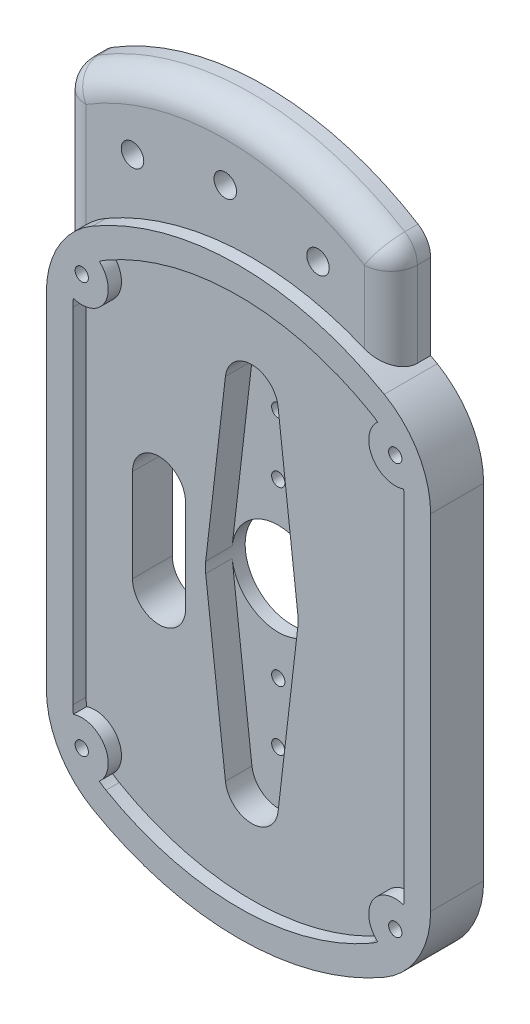
SolidWorks part; units mm, degrees
ref_plane "Спереди" through (0, 0, 0) normal (0, 0, 1) x (1, 0, 0)
ref_plane "Сверху" through (0, 0, 0) normal (0, 1, 0) x (1, 0, 0)
ref_plane "Справа" through (0, 0, 0) normal (1, 0, 0) x (0, 0, -1)
other "Configuration Table"
sketch "Эскиз1" plane through (0, 0, 0) normal (0, 0, 1) x (1, 0, 0)
  line L0 (-6.9532, 0.8077) -> (-3.9733, 26.4615)
  line L1 (3.9733, 26.4615) -> (6.9532, 0.8077)
  line L2 (0, 0) -> (45.5285, 0) construction
  line L3 (3.9733, -26.4615) -> (6.9532, -0.8077)
  line L4 (-6.9532, -0.8077) -> (-3.9733, -26.4615)
  line L5 (25, 25.9808) -> (25, -25.9808)
  line L6 (-25, -25.9808) -> (-25, 25.9808)
  line L7 (0, 0) -> (0, 67.5553) construction
  line L8 (-29, -25.9808) -> (-29, 25.9808)
  line L9 (29, 25.9808) -> (29, -25.9808)
  line L10 (-29, 25.9808) -> (-29, 53.6652)
  line L12 (21, 53.6652) -> (21, 38.6652)
  arc A0 (6.9532, -0.8077) -> (6.9532, 0.8077) centre (0, 0) ccw
  arc A1 (3.9733, 26.4615) -> (-3.9733, 26.4615) centre (0, 26) ccw
  arc A2 (-3.9733, -26.4615) -> (3.9733, -26.4615) centre (0, -26) ccw
  arc A3 (-6.9532, 0.8077) -> (-6.9532, -0.8077) centre (0, 0) ccw
  circle A4 centre (0, 0) radius 7
  circle A5 centre (0, 13) radius 1
  circle A6 centre (0, 22) radius 1
  circle A7 centre (0, -13) radius 1
  circle A8 centre (0, -22) radius 1
  arc A9 (-20, -34.641) -> (20, -34.641) centre (0, 0) ccw
  arc A10 (20, 34.641) -> (-20, 34.641) centre (0, 0) ccw
  arc A11 (-25, -25.9808) -> (-20, -34.641) centre (-15, -25.9808) ccw
  arc A12 (25, -25.9808) -> (20, -34.641) centre (15, -25.9808) cw
  arc A13 (25, 25.9808) -> (20, 34.641) centre (15, 25.9808) ccw
  arc A14 (-25, 25.9808) -> (-20, 34.641) centre (-15, 25.9808) cw
  arc A15 (-29, 25.9808) -> (-22, 38.1051) centre (-15, 25.9808) cw
  arc A16 (22, 38.1051) -> (-22, 38.1051) centre (0, 0) ccw
  arc A17 (29, 25.9808) -> (22, 38.1051) centre (15, 25.9808) ccw
  arc A18 (29, -25.9808) -> (22, -38.1051) centre (15, -25.9808) cw
  arc A19 (-22, -38.1051) -> (22, -38.1051) centre (0, 0) ccw
  arc A20 (-29, -25.9808) -> (-22, -38.1051) centre (-15, -25.9808) ccw
  circle A24 centre (-23.6603, 30.9808) radius 4
  circle A25 centre (23.6603, 30.9808) radius 4
  circle A26 centre (-23.6603, -30.9808) radius 4
  circle A27 centre (23.6603, -30.9808) radius 4
  circle A28 centre (-23.6603, 30.9808) radius 1
  circle A29 centre (23.6603, 30.9808) radius 1
  circle A30 centre (23.6603, -30.9808) radius 1
  circle A31 centre (-23.6603, -30.9808) radius 1
  arc A32 (-29, 53.6652) -> (21, 53.6652) centre (-4, 17.4575) cw
  point P33 (25, 31.225)
  dimension "D1" = 14
  dimension "D2" = 8
  dimension "D6" = 2
  dimension "D7" = 80
  dimension "D9" = 10
  dimension "D11" = 2
  dimension "D3" = 52
  dimension "D4" = 9
  dimension "D5" = 13
  dimension "D8" = 50
  dimension "D12" = 50
  dimension "D13" = 15
  dimension "D10" = 4
extrude "Бобышка-Вытянуть1" add sketch "Эскиз1" along normal blind 6 contours A14 L6 A11 A9 A12 L5 A13 A10 A3 L0 A1 L1 A0 L3 A2 L4 region at (24.0566, 0, 0)
extrude "Бобышка-Вытянуть2" add sketch "Эскиз1<3>" along normal blind 2 contours A4 L1 A1 L0 A6 A5 | A4 L4 A2 L3 A7 A8 region at (0, 16.3649, 0) region at (0, -16.3649, 0)
sketch "Эскиз1<3>" plane through (0, 0, 0) normal (0, 0, 1) x (1, 0, 0) same geometry as "Эскиз1"
extrude "Бобышка-Вытянуть3" add sketch "Эскиз1<4>" along normal blind 8 contours A31 A11 A26 | A31 A11 A26 | A26 A11 L6 A14 A24 A15 L8 A20 | A27 A12 A9 A11 A26 A20 A19 A18 | A30 A12 A27 | A30 A12 A27 | A27 A18 L9 A17 A25 A13 L5 A12 | A29 A13 A25 | A29 A13 A25 | A25 A17 A16 A15 A24 A14 A10 A13 | A28 A14 A24 | A28 A14 A24 region at (27.0355, 0, 0) region at (21.9856, 30.0139, 0) region at (25.0598, 31.7888, 0) region at (25.0598, -31.7888, 0) region at (21.9856, -30.0139, 0) region at (20.8192, 34.785, 0) region at (24.3908, -35.4754, 0) region at (-21.9856, 30.0139, 0) region at (-25.0598, 31.7888, 0) region at (-25.0598, -31.7888, 0) region at (-21.9856, -30.0139, 0) region at (-27.0355, 0, 0)
sketch "Эскиз1<4>" plane through (0, 0, 0) normal (0, 0, 1) x (1, 0, 0) same geometry as "Эскиз1"
sketch "Эскиз2" plane through (0, 0, 6) normal (0, 0, 1) x (1, 0, 0)
  line L0 (0.0013, 0.0008) -> (-44.6361, 0.0008) construction
  line L1 (-13.9987, -6.9992) -> (-13.9987, 7.0008) construction
  line L2 (-17.9987, -6.9992) -> (-17.9987, 7.0008)
  line L3 (-9.9987, -6.9992) -> (-9.9987, 7.0008)
  arc A0 (-17.9987, -6.9992) -> (-9.9987, -6.9992) centre (-13.9987, -6.9992) ccw
  arc A1 (-9.9987, 7.0008) -> (-17.9987, 7.0008) centre (-13.9987, 7.0008) ccw
  point P5 (-13.9987, 0.0008)
  dimension "D3" = 4
  dimension "D1" = 14
  dimension "D2" = 14
extrude "Вырез-Вытянуть1" cut sketch "Эскиз2" against normal through all
extrude "Бобышка-Вытянуть4" add sketch "Эскиз1<5>" along normal blind 6 contours A16 L12 A32 region at (-5.4153, 49.8916, 0)
sketch "Эскиз1<5>" plane through (0, 0, 0) normal (0, 0, 1) x (1, 0, 0) same geometry as "Эскиз1"
fillet "Скругление2" radius 4 5 edges at (-4, 61.4575, 6) (21, 46.1652, 6) (21, 53.6652, 3) (-29, 53.6652, 3) (-29, 39.823, 6)
hole_wizard "Отверстие с зазором M31" positions "Эскиз5" profile "Эскиз6" hole size "M3" standard "ISO"
sketch "Эскиз5" plane through (0, 0, 6) normal (0, 0, 1) x (1, 0, 0)
  line L0 (-4, 57.4575) -> (-4, 51.4575) construction
  arc A0 (-18, 48.4414) -> (10, 48.4414) centre (-4, 17.4575) cw construction
  arc A1 (17, 51.5016) -> (-25, 51.5016) centre (-4, 17.4575) ccw construction
  point P0 (-18, 48.4414)
  point P2 (-4, 51.4575)
  point P4 (10, 48.4414)
  dimension "D1" = 34
  dimension "D2" = 28
sketch "Эскиз6" plane through (-18, 48.4414, 6) normal (1, 0, 0) x (0, -1, 0)
  line L0 (0, 0) -> (0, 15)
  line L1 (0, 15) -> (1.7, 13.9785)
  line L2 (1.7, 13.9785) -> (1.7, 0)
  line L5 (1.7, 0) -> (0, 0)
  line L10 (0, 15) -> (-1.7, 13.9785) construction
  line L11 (0, -6.35) -> (0, 107.95) construction
  dimension "Диаметр отверстия" = 3.4
  dimension "Глубина отверстия" = 15
  dimension "Угол заточки сверла" = 118
